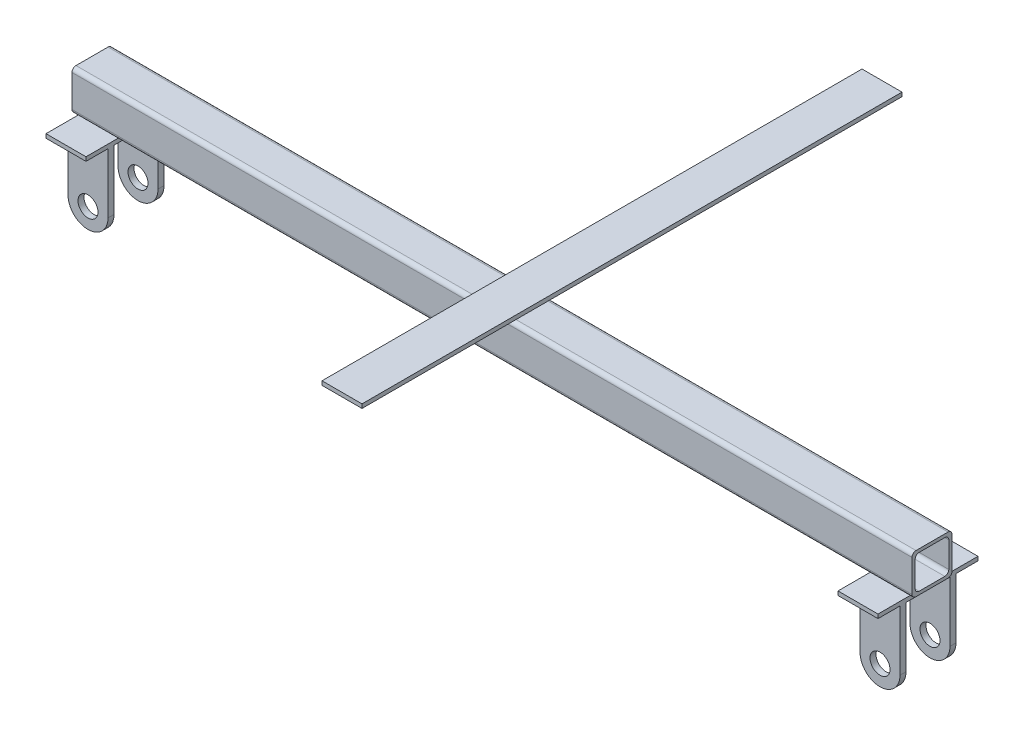
SolidWorks part; units mm, degrees
ref_plane "Front Plane" through (0, 0, 0) normal (0, 0, 1) x (1, 0, 0)
ref_plane "Top Plane" through (0, 0, 0) normal (0, 1, 0) x (1, 0, 0)
ref_plane "Right Plane" through (0, 0, 0) normal (1, 0, 0) x (0, 0, -1)
sketch "Sketch1" plane through (0, 0, 0) normal (0, 0, 1) x (1, 0, 0)
  line L0 (150, 0) -> (-150, 0) construction
  point P0 (0, 0)
  point P4 (0, 0)
  dimension "D1" = 300
sketch "Sketch2" plane through (0, 0, 0) normal (1, 0, 0) x (0, 0, -1)
  line L0 (-8.4, 8.4) -> (8.4, 8.4)
  line L1 (-10, -10) -> (10, -10)
  line L2 (-10, -10) -> (-10, 10)
  line L3 (-10, 10) -> (10, 10)
  line L4 (10, -10) -> (10, 10)
  line L5 (-10, -10) -> (10, 10) construction
  line L6 (-10, 10) -> (10, -10) construction
  line L7 (8.4, -8.4) -> (8.4, 8.4)
  line L8 (-8.4, -8.4) -> (8.4, -8.4)
  line L9 (-8.4, -8.4) -> (-8.4, 8.4)
  point P0 (0, 0)
  dimension "D1" = 20
  dimension "D2" = 1.6
extrude "Boss-Extrude1" add sketch "Sketch2" along direction (-1, 0, 0) on the side of the normal mid plane 420 contours L2 L1 L4 L3 | L0 L7 L8 L9
fillet "Fillet1" radius 2 8 edges at (0, 8.4, -8.4) (0, 8.4, 8.4) (0, -8.4, 8.4) (0, -8.4, -8.4) (0, -10, 10) (0, -10, -10) (0, 10, -10) (0, 10, 10)
sketch "Sketch3" plane through (0, -10, 0) normal (0, -1, 0) x (1, 0, 0)
  line L0 (-208, 0) -> (-188, 0) construction
  line L1 (-208, 25) -> (-188, 25)
  line L2 (-208, 25) -> (-208, -25)
  line L3 (-208, -25) -> (-188, -25)
  line L4 (-188, 25) -> (-188, -25)
  line L5 (188, 25) -> (208, 25)
  line L6 (188, 25) -> (188, -25)
  line L7 (188, -25) -> (208, -25)
  line L8 (208, 25) -> (208, -25)
  line L9 (188, 0) -> (208, 0) construction
  line L10 (150, 0) -> (-150, 0) construction
  line L11 (-210, 8) -> (-210, -8) construction
  line L12 (-210, -5.2851) -> (-208, -5.2851) construction
  line L13 (208, -4.2432) -> (210, -4.2432) construction
  line L14 (210, 8) -> (210, -8) construction
  dimension "D1" = 20
  dimension "D2" = 50
  dimension "D3" = 2
  dimension "D4" = 2
extrude "Boss-Extrude2" add sketch "Sketch3" along normal blind 2
sketch "Sketch4" plane through (0, -12, 0) normal (0, -1, 0) x (1, 0, 0)
  line L0 (-208, 25) -> (-208, -25) construction
  line L1 (-208, 14) -> (-188, 14)
  line L2 (-208, 14) -> (-208, 11)
  line L3 (-208, 11) -> (-188, 11)
  line L4 (-188, 14) -> (-188, 11)
  line L5 (-188, -25) -> (-188, 25) construction
  line L6 (188, 25) -> (188, -25) construction
  line L7 (-208, -11) -> (-188, -11)
  line L8 (-208, -11) -> (-208, -14)
  line L9 (-208, -14) -> (-188, -14)
  line L10 (-188, -11) -> (-188, -14)
  line L11 (188, 14) -> (208, 14)
  line L12 (188, 14) -> (188, 11)
  line L13 (188, 11) -> (208, 11)
  line L14 (208, 14) -> (208, 11)
  line L15 (208, -25) -> (208, 25) construction
  line L16 (-198, 0) -> (-198, 11) construction
  line L17 (188, -11) -> (208, -11)
  line L18 (188, -11) -> (188, -14)
  line L19 (188, -14) -> (208, -14)
  line L20 (208, -11) -> (208, -14)
  line L21 (150, 0) -> (-150, 0) construction
  line L22 (-198, 0) -> (-198, -11) construction
  line L23 (198, 11) -> (198, 0) construction
  line L24 (198, 0) -> (198, -11) construction
  dimension "D1" = 3
  dimension "D2" = 11
extrude "Boss-Extrude3" add sketch "Sketch4" along normal blind 40
fillet "Fillet2" radius 10 8 edges at (188, -52, 12.5) (208, -52, 12.5) (208, -52, -12.5) (188, -52, -12.5) (-188, -52, 12.5) (-188, -52, -12.5) (-208, -52, 12.5) (-208, -52, -12.5)
sketch "Sketch5" plane through (0, 0, 14) normal (0, 0, 1) x (1, 0, 0)
  circle A0 centre (-198, -42) radius 5
  circle A1 centre (198, -42) radius 5
  dimension "D1" = 10
extrude "Cut-Extrude1" cut sketch "Sketch5" against normal blind 40
sketch "Sketch6" plane through (0, 10, 0) normal (0, 1, 0) x (1, 0, 0)
  line L1 (10, -85) -> (-10, -85)
  line L2 (10, -85) -> (10, 185)
  line L3 (10, 185) -> (-10, 185)
  line L4 (-10, -85) -> (-10, 185)
  line L5 (10, -85) -> (-10, 185) construction
  line L6 (10, 185) -> (-10, -85) construction
  line L7 (210, -10) -> (-210, -10) construction
  point P0 (23.9726, 56.9806)
  point P9 (0, 50)
  dimension "D1" = 20
  dimension "D2" = 270
  dimension "D3" = 75
extrude "Boss-Extrude4" add sketch "Sketch6" along normal blind 2
